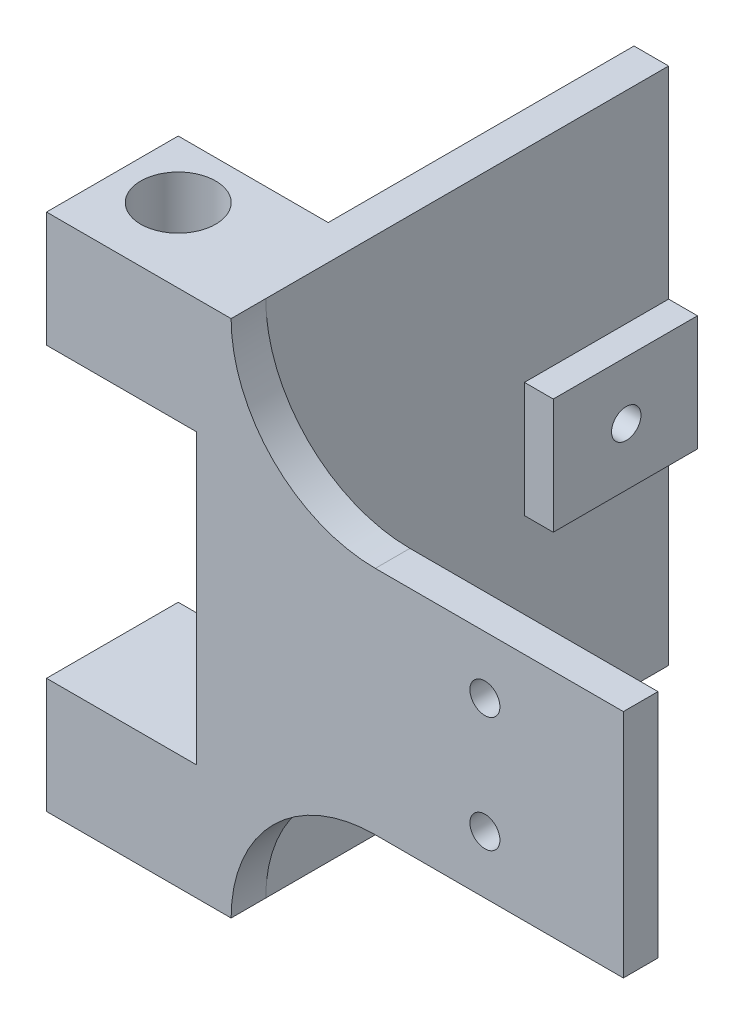
SolidWorks part; units mm, degrees
ref_plane "Front Plane" through (0, 0, 0) normal (0, 0, 1) x (1, 0, 0)
ref_plane "Top Plane" through (0, 0, 0) normal (0, 1, 0) x (1, 0, 0)
ref_plane "Right Plane" through (0, 0, 0) normal (1, 0, 0) x (0, 0, -1)
sketch "Sketch1" plane through (0, 0, 0) normal (0, 0, 1) x (1, 0, 0)
  line L1 (0, 0) -> (74, 0)
  line L2 (0, 0) -> (0, 90)
  line L3 (0, 90) -> (74, 90)
  line L4 (74, 0) -> (74, 90)
  circle A0 centre (50, 55) radius 2.6
  circle A1 centre (50, 35) radius 2.6
  dimension "D3" = 5.2
  dimension "D4" = 5.2
  dimension "D1" = 90
  dimension "D2" = 74
  dimension "D5" = 50
  dimension "D6" = 50
  dimension "D7" = 20
  dimension "D8" = 35
extrude "Boss-Extrude1" add sketch "Sketch1" along normal blind 6
sketch "Sketch2" plane through (0, 0, 0) normal (0, 0, -1) x (-1, 0, 0)
  line L0 (0, 0) -> (-74, 0) construction
  line L1 (0, 90) -> (-6, 90)
  line L2 (0, 90) -> (0, 0)
  line L3 (0, 0) -> (-6, 0)
  line L4 (-6, 90) -> (-6, 0)
  dimension "D1" = 6
extrude "Boss-Extrude2" add sketch "Sketch2" along normal blind 69.85
sketch "Sketch4" plane through (0, 0, 0) normal (0, 0, -1) x (-1, 0, 0)
  line L0 (-6, 90) -> (-6, 0) construction
  line L1 (-74, 90) -> (-6, 90)
  line L2 (-74, 90) -> (-74, 65)
  line L3 (-74, 65) -> (-6, 65)
  line L4 (-6, 90) -> (-6, 65)
  line L5 (-6, 90) -> (-6, 0) construction
  line L6 (-74, 0) -> (-6, 0)
  line L7 (-74, 0) -> (-74, 25)
  line L8 (-74, 25) -> (-6, 25)
  line L9 (-6, 0) -> (-6, 25)
  dimension "D1" = 25
  dimension "D2" = 25
extrude "Cut-Extrude3" cut sketch "Sketch4" against normal blind 6
fillet "Fillet2" radius 25 2 edges at (6, 65, 3) (6, 25, 3)
sketch "Sketch8" plane through (0, 0, 0) normal (-1, 0, 0) x (0, 0, 1)
  line L0 (6, 90) -> (6, 0) construction
  line L1 (6, 0) -> (-16.83, 0)
  line L2 (6, 0) -> (6, 20)
  line L3 (6, 20) -> (-16.83, 20)
  line L4 (-16.83, 0) -> (-16.83, 20)
  line L5 (6, 90) -> (-43, 90) construction
  line L6 (-16.83, 70) -> (6, 70)
  line L7 (-16.83, 70) -> (-16.83, 90)
  line L8 (-16.83, 90) -> (6, 90)
  line L9 (6, 70) -> (6, 90)
  dimension "D1" = 20
  dimension "D2" = 0
  dimension "D3" = 22.83
  dimension "D4" = 0
  dimension "D5" = 0
  dimension "D6" = 20
  dimension "D7" = 22.83
extrude "Boss-Extrude4" add sketch "Sketch8" along normal blind 26
sketch "Sketch9" plane through (0, 0, 0) normal (0, -1, 0) x (1, 0, 0)
  line L0 (-26, -16.83) -> (0, -16.83) construction
  line L1 (-26, -16.83) -> (-26, 6) construction
  circle A0 centre (-16, -6.83) radius 6.5
  dimension "D1" = 13
  dimension "D2" = 10
  dimension "D3" = 10
extrude "Cut-Extrude6" cut sketch "Sketch9" against normal blind 10
sketch "Sketch10" plane through (0, 90, 0) normal (0, 1, 0) x (1, 0, 0)
  line L0 (-26, -6) -> (-26, 16.83) construction
  line L1 (-26, 16.83) -> (0, 16.83) construction
  circle A0 centre (-16, 6.83) radius 6.5
  dimension "D1" = 13
  dimension "D2" = 10
  dimension "D3" = 10
extrude "Cut-Extrude7" cut sketch "Sketch10" against normal blind 10
sketch "Sketch11" plane through (0, 0, 0) normal (-1, 0, 0) x (0, 0, 1)
  line L0 (-16.83, 90) -> (-69.85, 90) construction
  line L1 (6, 70) -> (6, 20) construction
  circle A0 centre (-57.5, 45) radius 6.35
  dimension "D2" = 63.5
  dimension "D3" = 12.7
  dimension "D1" = 45
extrude "Cut-Extrude8" cut sketch "Sketch11" against normal blind 4.9784
sketch "Sketch12" plane through (6, 0, 0) normal (1, 0, 0) x (0, 0, -1)
  line L0 (69.85, 90) -> (69.85, 0) construction
  line L1 (44.85, 55) -> (69.85, 55)
  line L2 (44.85, 55) -> (44.85, 35)
  line L3 (44.85, 35) -> (69.85, 35)
  line L4 (69.85, 55) -> (69.85, 35)
  line L5 (69.85, 90) -> (0, 90) construction
  dimension "D1" = 20
  dimension "D2" = 35
  dimension "D3" = 25
extrude "Boss-Extrude5" add sketch "Sketch12" along normal blind 5
sketch "Sketch13" plane through (4.9784, 0, 0) normal (-1, 0, 0) x (0, 0, 1)
  circle A0 centre (-57.5, 45) radius 2.55
  circle A1 centre (-57.5, 45) radius 6.35 construction
  dimension "D1" = 5.1
  dimension "D2" = 0
extrude "Cut-Extrude9" cut sketch "Sketch13" against normal through all both and the other way through all
equation "\"D6@Sketch1\"=\"D5@Sketch1\""
equation "\"D8@Sketch1\"=(\"D1@Sketch1\"-\"D7@Sketch1\")/2"
equation "\"D3@Sketch7\"=(30-\"D1@Sketch7\")/2"
